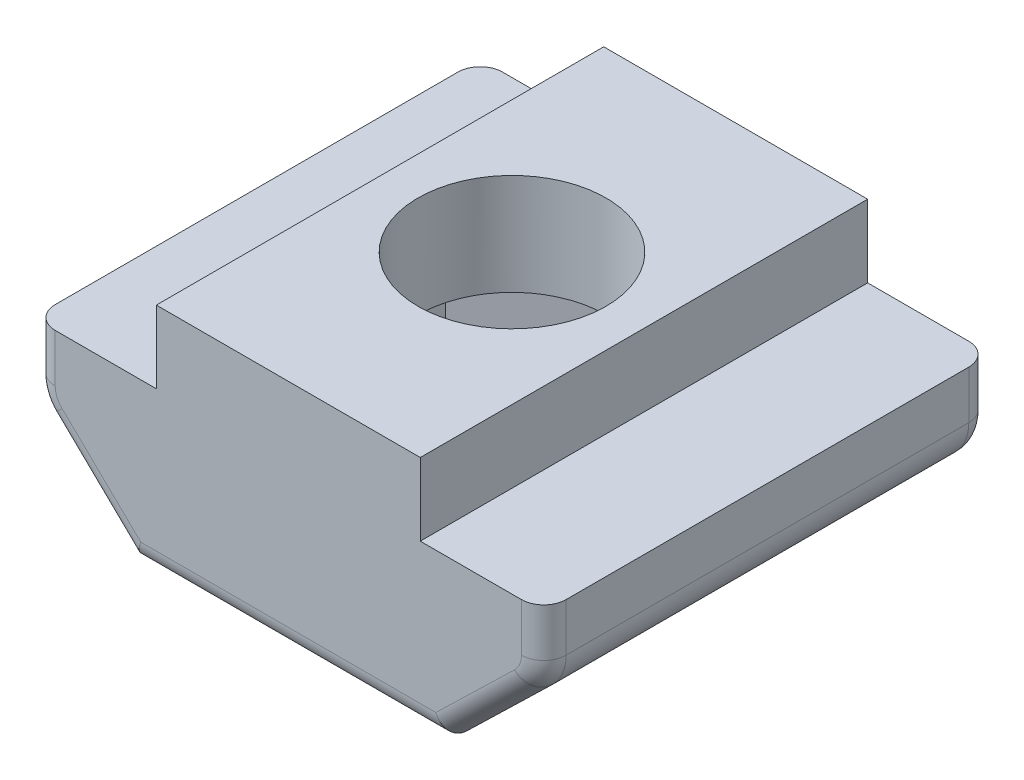
SolidWorks part; units mm, degrees
ref_plane "Plan de face" through (0, 0, 0) normal (0, 0, 1) x (1, 0, 0)
ref_plane "Plan de dessus" through (0, 0, 0) normal (0, 1, 0) x (1, 0, 0)
ref_plane "Plan de droite" through (0, 0, 0) normal (1, 0, 0) x (0, 0, -1)
sketch "Esquisse1" plane through (0, 0, 0) normal (0, 0, 1) x (1, 0, 0)
  line L0 (0, 4) -> (0, 14.517) construction
  line L1 (-2.95, 10.1031) -> (2.95, 10.1031)
  line L22 (2.95, 10.1031) -> (2.95, 8.4831)
  line L23 (2.95, 8.4831) -> (5.71, 8.4831)
  line L24 (5.71, 8.4831) -> (5.71, 6.9831)
  line L25 (5.71, 6.9831) -> (3.5, 4.84)
  line L26 (3.5, 4.84) -> (-3.5, 4.84)
  line L27 (-5.71, 6.9831) -> (-3.5, 4.84)
  line L28 (-5.71, 8.4831) -> (-5.71, 6.9831)
  line L29 (-2.95, 8.4831) -> (-5.71, 8.4831)
  line L30 (-2.95, 10.1031) -> (-2.95, 8.4831)
  point P10 (0, 4.84)
  point P14 (0, 10.1031)
  point P41 (0, 0)
  point P46 (0, 0)
  line B0 (0, 0) -> (0, 4) construction
  line B1 (0, 4) -> (0.866, 4.5)
  line B2 (0, 4) -> (-0.866, 4.5)
  line B3 (0.866, 4.5) -> (3.4393, 4.5)
  line B4 (3.4393, 4.5) -> (6, 7.0607)
  line B5 (6, 7.0607) -> (6, 8.5)
  line B6 (6, 8.5) -> (3, 8.5)
  line B7 (3, 8.5) -> (3, 9.5)
  line B8 (3, 9.5) -> (3.5, 9.5)
  line B9 (3.5, 9.5) -> (3.5, 10)
  line B10 (3.5, 10) -> (8.5, 10)
  line B11 (0, 0) -> (1.2745, 0) construction
  line B12 (-3.5, -10) -> (-8.5, -10)
  line B13 (-3.4393, -4.5) -> (-6, -7.0607)
  line B14 (-3.5, 9.5) -> (-3.5, 10)
  line B15 (-3, 9.5) -> (-3.5, 9.5)
  line B16 (-3, 8.5) -> (-3, 9.5)
  line B17 (-6, 8.5) -> (-3, 8.5)
  line B18 (-6, 7.0607) -> (-6, 8.5)
  line B19 (-0.866, 4.5) -> (-3.4393, 4.5)
  line B20 (-3.4393, 4.5) -> (-6, 7.0607)
  line B21 (-3.5, 10) -> (-8.5, 10)
  line B22 (-0.866, -4.5) -> (-3.4393, -4.5)
  line B23 (-6, -7.0607) -> (-6, -8.5)
  line B24 (-6, -8.5) -> (-3, -8.5)
  line B25 (-3, -8.5) -> (-3, -9.5)
  line B26 (-3, -9.5) -> (-3.5, -9.5)
  line B27 (-3.5, -9.5) -> (-3.5, -10)
  line B28 (3.5, -10) -> (8.5, -10)
  line B29 (3.5, -9.5) -> (3.5, -10)
  line B30 (3, -9.5) -> (3.5, -9.5)
  line B31 (3, -8.5) -> (3, -9.5)
  line B32 (6, -8.5) -> (3, -8.5)
  line B33 (6, -7.0607) -> (6, -8.5)
  line B34 (3.4393, -4.5) -> (6, -7.0607)
  line B35 (0.866, -4.5) -> (3.4393, -4.5)
  line B36 (0, -4) -> (-0.866, -4.5)
  line B37 (0, -4) -> (0.866, -4.5)
  line B38 (10, -3.5) -> (10, -8.5)
  line B39 (9.5, -3.5) -> (10, -3.5)
  line B40 (8.5, -3) -> (9.5, -3)
  line B41 (9.5, -3) -> (9.5, -3.5)
  line B42 (8.5, -6) -> (8.5, -3)
  line B43 (7.0607, -6) -> (8.5, -6)
  line B44 (4.5, -3.4393) -> (7.0607, -6)
  line B45 (4.5, -0.866) -> (4.5, -3.4393)
  line B46 (4.5, 0.866) -> (4.5, 3.4393)
  line B47 (4.5, 3.4393) -> (7.0607, 6)
  line B48 (7.0607, 6) -> (8.5, 6)
  line B49 (8.5, 6) -> (8.5, 3)
  line B50 (8.5, 3) -> (9.5, 3)
  line B51 (9.5, 3) -> (9.5, 3.5)
  line B52 (9.5, 3.5) -> (10, 3.5)
  line B53 (10, 3.5) -> (10, 8.5)
  line B54 (-3.5, -9.5) -> (-3.5, -10)
  line B55 (-3, -8.5) -> (-3, -9.5)
  line B56 (-3, -9.5) -> (-3.5, -9.5)
  line B57 (-6, -8.5) -> (-3, -8.5)
  line B58 (-6, -7.0607) -> (-6, -8.5)
  line B59 (-3.4393, -4.5) -> (-6, -7.0607)
  line B60 (-0.866, -4.5) -> (-3.4393, -4.5)
  line B61 (0.866, -4.5) -> (3.4393, -4.5)
  line B62 (3.4393, -4.5) -> (6, -7.0607)
  line B63 (6, -7.0607) -> (6, -8.5)
  line B64 (6, -8.5) -> (3, -8.5)
  line B65 (3, -8.5) -> (3, -9.5)
  line B66 (3, -9.5) -> (3.5, -9.5)
  line B67 (3.5, -9.5) -> (3.5, -10)
  line B68 (-10, 3.5) -> (-10, 8.5)
  line B69 (-9.5, 3.5) -> (-10, 3.5)
  line B70 (-8.5, 3) -> (-9.5, 3)
  line B71 (-9.5, 3) -> (-9.5, 3.5)
  line B72 (-8.5, 6) -> (-8.5, 3)
  line B73 (-7.0607, 6) -> (-8.5, 6)
  line B74 (-4.5, 3.4393) -> (-7.0607, 6)
  line B75 (-4.5, 0.866) -> (-4.5, 3.4393)
  line B76 (-4.5, -0.866) -> (-4.5, -3.4393)
  line B77 (-4.5, -3.4393) -> (-7.0607, -6)
  line B78 (-7.0607, -6) -> (-8.5, -6)
  line B79 (-8.5, -6) -> (-8.5, -3)
  line B80 (-8.5, -3) -> (-9.5, -3)
  line B81 (-9.5, -3) -> (-9.5, -3.5)
  line B82 (-9.5, -3.5) -> (-10, -3.5)
  line B83 (-10, -3.5) -> (-10, -8.5)
  line B84 (4, 0) -> (4.5, -0.866)
  line B85 (4, 0) -> (4.5, 0.866)
  line B86 (0, -4) -> (-0.866, -4.5)
  line B87 (0, -4) -> (0.866, -4.5)
  line B88 (-4, 0) -> (-4.5, 0.866)
  line B89 (-4, 0) -> (-4.5, -0.866)
  line B90 (0, 0) -> (1.9445, 1.9445) construction
  arc B91 (8.5, 10) -> (10, 8.5) centre (8.5, 8.5) cw
  arc B92 (-8.5, 10) -> (-10, 8.5) centre (-8.5, 8.5) ccw
  arc B93 (-8.5, -10) -> (-10, -8.5) centre (-8.5, -8.5) cw
  arc B94 (8.5, -10) -> (10, -8.5) centre (8.5, -8.5) ccw
  circle B95 centre (0, 0) radius 2.75
  dimension "D1" = 2.95
  dimension "D2" = 1.62
  dimension "D3" = 2.76
  dimension "D4" = 1.5
  dimension "D5" = 135.88
  dimension "D6" = 3.5
  dimension "D7" = 0.34
sketch_block_instance "Bloc1-1"
sketch_block "Bloc1"
extrude "Boss.-Extru.1" add sketch "Esquisse1" against normal blind 10 contours L0 L26 L25 L24 L23 L22 L1 | L26 L0 L1 L30 L29 L28 L27 region at (-2.3548, 7.3163, 0) region at (2.3548, 7.3163, 0)
fillet "Congé1" radius 0.5 10 edges at (0, 4.84, -10) (-4.605, 5.9116, -10) (-5.71, 7.7331, -10) (4.605, 5.9116, -10) (5.71, 7.7331, -10) (-5.71, 7.7331, 0) (-4.605, 5.9116, 0) (0, 4.84, 0) (4.605, 5.9116, 0) (5.71, 7.7331, 0)
fillet "Congé2" radius 1 6 edges at (5.5636, 7.0451, -0.1464) (5.5636, 7.0451, -9.8536) (-5.5636, 7.0451, -0.1464) (-5.5636, 7.0451, -9.8536) (-5.71, 6.9831, -5) (5.71, 6.9831, -5)
sketch "Esquisse2" plane through (0, 10.1031, 0) normal (0, 1, 0) x (1, 0, 0)
  line L0 (0, 0) -> (0, 10) construction
  line L1 (-2.95, 10) -> (2.95, 10) construction
  circle A0 centre (0, 5) radius 2.1
  dimension "D1" = 4.2
extrude "Enlèv. mat.-Extru.1" cut sketch "Esquisse2" against normal through all
sketch "Esquisse3" plane through (0, 4.84, 0) normal (0, -1, 0) x (1, 0, 0)
  line L0 (0, -5) -> (0, -4.1016) construction
  line L1 (0, -9.05) -> (3.5074, -7.025)
  line L2 (3.5074, -7.025) -> (3.5074, -2.975)
  line L3 (3.5074, -2.975) -> (0, -0.95)
  line L4 (0, -0.95) -> (-3.5074, -2.975)
  line L5 (-3.5074, -2.975) -> (-3.5074, -7.025)
  line L6 (-3.5074, -7.025) -> (0, -9.05)
  line L7 (0, -5) -> (-0.7318, -5) construction
  circle A0 centre (0, -5) radius 4.05 construction
  dimension "D1" = 8.1
extrude "Enlèv. mat.-Extru.2" cut sketch "Esquisse3" against normal blind 3
